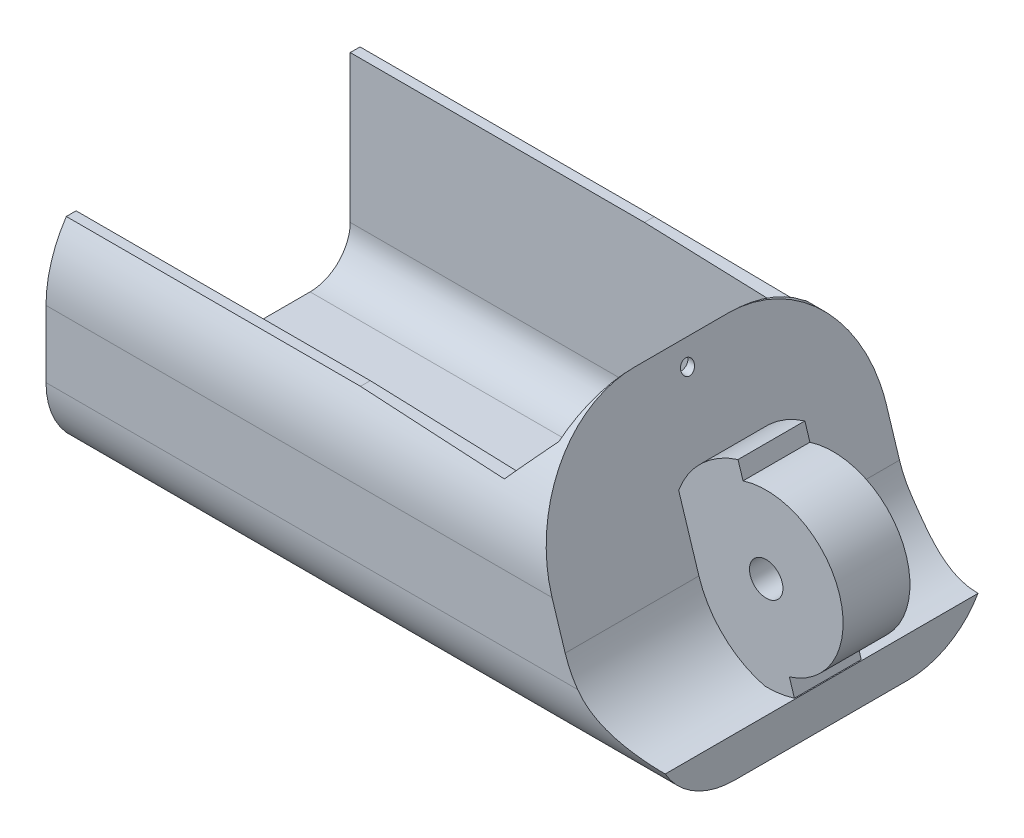
SolidWorks part; units mm, degrees
ref_plane "Alzado" through (0, 0, 0) normal (0, 0, 1) x (1, 0, 0)
ref_plane "Planta" through (0, 0, 0) normal (0, 1, 0) x (1, 0, 0)
ref_plane "Vista lateral" through (0, 0, 0) normal (1, 0, 0) x (0, 0, -1)
sketch "Croquis1" plane through (0, 0, 0) normal (0, 0, 1) x (1, 0, 0)
  line L1 (-52.5, -20) -> (52.5, -20)
  line L2 (-52.5, -20) -> (-52.5, 20)
  line L3 (-52.5, 20) -> (52.5, 20)
  line L4 (52.5, -20) -> (52.5, 20)
  line L5 (-52.5, -20) -> (52.5, 20) construction
  line L6 (-52.5, 20) -> (52.5, -20) construction
  point P0 (0, 0)
  dimension "D1" = 105
  dimension "D2" = 40
extrude "Saliente-Extruir1" add sketch "Croquis1" along normal mid plane 50
sketch "Croquis2" plane through (0, 0, 25) normal (0, 0, 1) x (1, 0, 0)
  line L0 (-52.5, 12) -> (-46.5, 12)
  line L1 (-52.5, 20) -> (-52.5, -20) construction
  line L2 (-46.5, 12) -> (-46.5, 6)
  line L3 (-46.5, 6) -> (-26.5, 6)
  line L4 (-26.5, 6) -> (-26.5, 12)
  line L5 (-26.5, 12) -> (-8.5, 12)
  line L6 (-8.5, 12) -> (-8.5, 6)
  line L7 (-8.5, 6) -> (13.5, 6)
  line L8 (13.5, 6) -> (13.5, 11.2419)
  line L9 (13.5, 11.2419) -> (17.5, 16)
  line L10 (17.5, 16) -> (17.5, 20)
  line L11 (52.5, 20) -> (-52.5, 20) construction
  line L12 (-52.5, 12) -> (-52.5, 20)
  line L13 (-52.5, 20) -> (17.5, 20)
  line L14 (-52.5, -20) -> (52.5, -20) construction
  line L15 (39.5, 0) -> (0, 0) construction
  line L16 (52.5, -20) -> (52.5, 20) construction
  line L17 (-46.5, 12) -> (-26.5, 12)
  line L18 (-8.5, 12) -> (13.5, 11.2419)
  line L19 (-46.5, 12) -> (-26.5, 12)
  circle A0 centre (39.5, 0) radius 13 construction
  point P4 (17.5, 18)
  line M14 (52.5, 20) -> (-52.5, 20)
  line M15 (-52.5, 20) -> (-52.5, -20)
  dimension "D10" = 26
  dimension "D1" = 6
  dimension "D2" = 70
  dimension "D3" = 18
  dimension "D4" = 20
  dimension "D5" = 6
  dimension "D6" = 26
  dimension "D7" = 4
  dimension "D8" = 4
  dimension "D9" = 4.7581
extrude "Cortar-Extruir1" cut sketch "Croquis2" against normal blind 50 contours L5 L18 L9 L10 L0 L17 M14 M15 region at (-17.5408, 15.967, 25)
sketch "Croquis5" plane through (0, 0, 25) normal (0, 0, 1) x (1, 0, 0)
  line L0 (-21.8249, 0) -> (71.7691, 0) construction
  line L1 (52.5, -20) -> (17.5, -20) construction
  line L2 (52.5, 0) -> (52.5, 20) construction
  line L3 (52.5, 20) -> (17.5, 20) construction
  line L4 (17.5, -20) -> (17.5, 20) construction
  line L5 (17.5, 20) -> (25.1503, -4.2172)
  line L6 (17.5, 20) -> (52.5, 20)
  line L7 (52.5, 20) -> (52.5, 0)
  line L9 (52.5, -20) -> (30.1361, -20)
  line L10 (52.5, -20) -> (52.5, 20) construction
  line L11 (38.5, -14) -> (52.5, -14)
  line L12 (52.5, -14) -> (52.5, 0)
  arc A0 (52.5, 0) -> (38.5, -14) centre (38.5, 0) ccw
  arc A1 (38.5, -14) -> (52.5, 0) centre (38.5, 0) ccw
  line M2 (52.5, 20) -> (17.5, 20)
  line M15 (52.5, -20) -> (52.5, 20)
  dimension "D1" = 28
extrude "Cortar-Extruir2" cut sketch "Croquis5" against normal blind 50 contours A0 L5 M15 M2 | A0 region at (34.6505, 14.3929, 25) region at (38.5, 0, 25)
sketch "Croquis6" plane through (0, 0, 0) normal (0, 0, 1) x (1, 0, 0)
  line L0 (30.0802, 16.6941) -> (40.1499, -15.1819) construction
  line L1 (17.5, 20) -> (25.1503, -4.2172) construction
  line L2 (38.6808, -10.5315) -> (39.4339, -12.9154)
  line L3 (31.7525, 11.4002) -> (30.9995, 13.784)
  circle A0 centre (35.2167, 0.4343) radius 14
  circle A1 centre (35.2167, 0.4343) radius 11.5
  circle A2 centre (35.2167, 0.4343) radius 2.5
  dimension "D1" = 28
  dimension "D3" = 23
  dimension "D5" = 5
  dimension "D2" = 11
  dimension "D4" = 35.2167
extrude "Saliente-Extruir3" add sketch "Croquis6" along normal mid plane 10 contours A1 L0 A2 | L0 A1 A2 | A1 L3 A0 L2 region at (23.9375, -3.1288, 0) region at (40.0514, 1.9616, 0) region at (30.3819, -1.093, 0)
sketch "Croquis8" plane through (0, 0, 25) normal (0, 0, 1) x (1, 0, 0)
  line L1 (-52.5, -20) -> (52.5, -20) construction
  line L2 (38.5, -20) -> (38.5, -14)
  line L8 (17.5, 20) -> (17.5, 16)
  line L9 (17.5, 16) -> (13.5, 11.2419)
  line L13 (-8.5, 12) -> (-52.5, 12)
  line L14 (13.5, 11.2419) -> (-8.5, 12)
  line L15 (13.5, 11.2419) -> (-8.5, 12)
  line L16 (25.1503, -4.2172) -> (17.5, 20)
  line L27 (-52.5, 12) -> (-52.5, -20)
  line L28 (-52.5, -20) -> (52.5, -20)
  line L29 (52.5, -20) -> (52.5, 0)
  line L42 (38.5, -20) -> (52.5, -20)
  line L43 (52.5, -20) -> (52.5, 0)
  arc A2 (25.1503, -4.2172) -> (52.5, 0) centre (38.5, 0) ccw
  arc A4 (38.5, -14) -> (52.5, 0) centre (38.5, 0) ccw
  line M30 (-52.5, -20) -> (52.5, -20)
  line M31 (52.5, -20) -> (52.5, 0)
  arc M32 (52.5, 0) -> (25.1503, -4.2172) centre (38.5, 0) cw
  dimension "D1" = 0
extrude "Cortar-Extruir3" cut sketch "Croquis8" against normal through all contours L2 M30 M31 M32 region at (46.7922, -14.9556, 25)
fillet "Redondeo2" radius 12 2 edges at (-7, -20, -25) (-7, -20, 25)
sketch "Croquis10" plane through (-52.5, 0, 0) normal (-1, 0, 0) x (0, 0, 1)
  line L0 (-25, 12) -> (-25, -8) construction
  line L1 (-25, 32) -> (25, 32)
  line L2 (-25, 32) -> (-25, 0)
  line L3 (-25, 0) -> (25, 0)
  line L4 (25, 32) -> (25, 0)
  line L5 (25, 12) -> (25, -8) construction
  line L8 (-25, 0) -> (-25, 2)
  line L9 (-7, 20) -> (7, 20)
  line L10 (25, 0) -> (25, 2)
  line L11 (-21.9512, -17.561) -> (25, 20) construction
  line L12 (-25, 20) -> (21.9512, -17.561) construction
  line L13 (-25, 12) -> (25, 12) construction
  line L14 (-25, 20) -> (25, 20) construction
  arc A1 (7, 20) -> (25, 2) centre (7, 2) cw
  arc A2 (-25, 2) -> (-7, 20) centre (-7, 2) cw
  point P8 (0, 12)
  line M15 (-25, 12) -> (-25, -8)
  line M20 (25, 12) -> (-25, 12)
  dimension "D1" = 18
  dimension "D2" = 32
extrude "Cortar-Extruir4" cut sketch "Croquis10" against normal blind 110 contours A2 M15 M20 | A2 L9 A1 L4 L1 L2 M20 | A1 L4 M20 region at (-52.5, 24.5091, 0) region at (-52.5, 9.5441, -24.1048) region at (-52.5, 9.5441, 24.1048)
sketch "Croquis11" plane through (-52.5, 0, 0) normal (-1, 0, 0) x (0, 0, 1)
  line L0 (0, 9.5473) -> (0, -17.1641) construction
  line L1 (-20.5, 23.7724) -> (20.5, 23.7724)
  line L2 (-20.5, 23.7724) -> (-20.5, -10)
  line L3 (-14.5, -16) -> (14.5, -16)
  line L4 (20.5, 23.7724) -> (20.5, -10)
  line L5 (13, -20) -> (-13, -20) construction
  arc A0 (14.5, -16) -> (20.5, -10) centre (14.5, -10) ccw
  arc A1 (-20.5, -10) -> (-14.5, -16) centre (-14.5, -10) ccw
  point P9 (20.5, -16)
  point P12 (-20.5, -16)
  line M10 (21.9666, 12) -> (-21.9666, 12)
  dimension "D2" = 6
  dimension "D1" = 41
  dimension "D3" = 4
  dimension "D4" = 33.7724
extrude "Cortar-Extruir5" cut sketch "Croquis11" against normal blind 66 contours L2 A1 L3 A0 L4 M10 | L4 L1 L2 M10 region at (-52.5, 17.8862, 0) region at (-52.5, -1.8273, 0)
sketch "Croquis12" plane through (0, 0, 0) normal (0, 0, 1) x (1, 0, 0)
  line L4 (-52.5, -28) -> (-32.5, -28)
  line L12 (-50.1656, -23) -> (-34.8344, -23)
  line L21 (-50.1656, -23) -> (-50.1656, -26)
  line L22 (-50.1656, -26) -> (-34.8344, -26)
  line L23 (-34.8344, -23) -> (-34.8344, -26)
  line L24 (-32.5, -20) -> (-32.5, -28)
  line L25 (-52.5, -20) -> (-32.5, -20)
  line L26 (-52.5, -20) -> (-52.5, -28)
  line L27 (38.5, -20) -> (-52.5, -20) construction
  line L28 (38.5, -20) -> (-52.5, -20)
  line L29 (-52.5, -8) -> (-52.5, -20) construction
  line L30 (-20.5, -35.1473) -> (-20.5, -3.279) construction
  line L31 (11.5, -20) -> (11.5, -28)
  line L32 (11.5, -20) -> (-8.5, -20)
  line L33 (-8.5, -20) -> (-8.5, -28)
  line L34 (-6.1656, -23) -> (-6.1656, -26)
  line L35 (9.1656, -26) -> (-6.1656, -26)
  line L36 (9.1656, -23) -> (9.1656, -26)
  line L37 (9.1656, -23) -> (-6.1656, -23)
  line L38 (11.5, -28) -> (-8.5, -28)
  spline S0 degree 2 poles (-32.5, -24) (-20.5, -16) (-8.5, -24) knots 0 0 0 1 1 1
  dimension "D1" = 3
  dimension "D2" = 3
  dimension "D3" = 20
  dimension "D4" = 32
  dimension "D5" = 2
  dimension "D6" = 2.3344
  dimension "D7" = 2.3344
  dimension "D8" = 2.3344
  dimension "D9" = 2.3344
extrude "Saliente-Extruir4" add sketch "Croquis12" along normal mid plane 5 contours L25 L26 L4 L24 L12 L23 L22 L21 | L38 L31 L28 L33 L37 L36 L35 L34 | L24 S0 L28 | L28 S0 L33
sketch "Croquis13" plane through (17.5, 0, 0) normal (-1, 0, 0) x (0, 0, 1)
  line L0 (0, -4.4034) -> (0, 22.2086) construction
  circle A0 centre (0, 17) radius 1
  dimension "D1" = 2
  dimension "D2" = 17
extrude "Cortar-Extruir6" cut sketch "Croquis13" against normal blind 10
fillet "Redondeo3" radius 2 4 edges at (-8.5, -28, 0) (-52.5, -28, 0) (-32.5, -28, 0) (11.5, -28, 0)
fillet "Redondeo4" radius 2 1 edges at (11.5, -20, 0)
fillet "Redondeo5" radius 1 8 edges at (-34.8344, -26, 0) (-50.1656, -26, 0) (-50.1656, -23, 0) (-34.8344, -23, 0) (-6.1656, -26, 0) (-6.1656, -23, 0) (9.1656, -26, 0) (9.1656, -23, 0)
